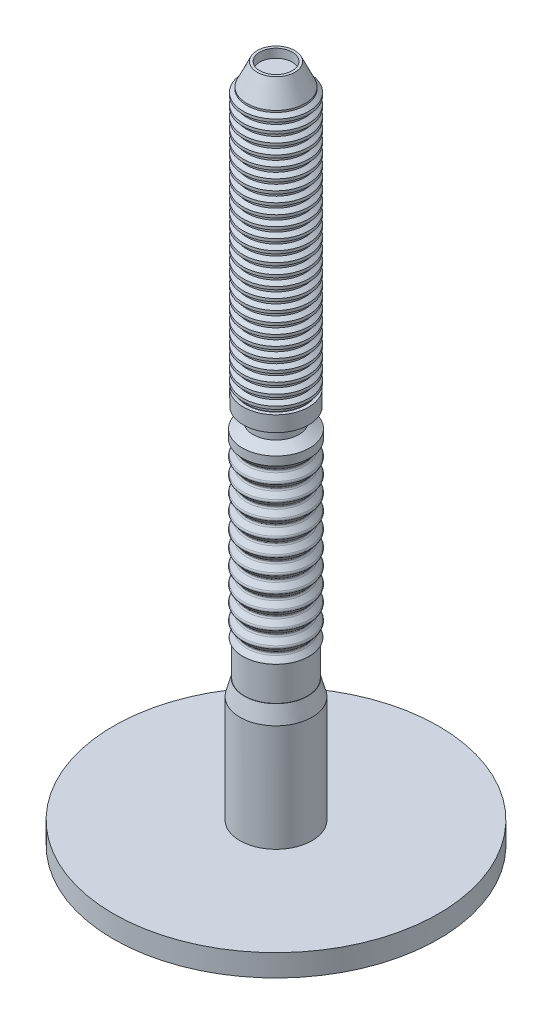
SolidWorks part; units mm, degrees
ref_plane "Front Plane" through (0, 0, 0) normal (0, 0, 1) x (1, 0, 0)
ref_plane "Top Plane" through (0, 0, 0) normal (0, 1, 0) x (1, 0, 0)
ref_plane "Right Plane" through (0, 0, 0) normal (1, 0, 0) x (0, 0, -1)
sketch "Sketch1" plane through (0, 0, 0) normal (0, 1, 0) x (1, 0, 0)
  circle A0 centre (0, 0) radius 18.5
  dimension "D1" = 37
extrude "Boss-Extrude1" add sketch "Sketch1" along normal blind 2.5
sketch "Sketch2" plane through (0, 2.5, 0) normal (0, 1, 0) x (1, 0, 0)
  circle A0 centre (0, 0) radius 4.1
  dimension "D1" = 8.2
extrude "Boss-Extrude2" add sketch "Sketch2" along normal blind 14
sketch "Sketch3" plane through (0, 16.5, 0) normal (0, 1, 0) x (1, 0, 0)
  circle A0 centre (0, 0) radius 3.575
  dimension "D1" = 7.15
extrude "Boss-Extrude3" add sketch "Sketch3" along normal blind 4
sketch "Sketch4" plane through (0, 20.5, 0) normal (0, 1, 0) x (1, 0, 0)
  circle A0 centre (0, 0) radius 3.825
  dimension "D1" = 7.65
extrude "Boss-Extrude4" add sketch "Sketch4" along normal blind 21.3
sketch "Sketch5" plane through (0, 41.8, 0) normal (0, 1, 0) x (1, 0, 0)
  circle A0 centre (0, 0) radius 2.6
  dimension "D1" = 5.2
extrude "Boss-Extrude5" add sketch "Sketch5" along normal blind 0.75
sketch "Sketch6" plane through (0, 42.55, 0) normal (0, 1, 0) x (1, 0, 0)
  circle A0 centre (0, 0) radius 3.725
  dimension "D1" = 7.45
extrude "Boss-Extrude6" add sketch "Sketch6" along normal blind 2.5
sketch "Sketch7" plane through (0, 45.05, 0) normal (0, 1, 0) x (1, 0, 0)
  circle A0 centre (0, 0) radius 3.75
  dimension "D1" = 7.5
extrude "Boss-Extrude7" add sketch "Sketch7" along normal blind 32.2
chamfer "Chamfer2" distance 0.739 angle 60 1 edges at (0, 41.8, 3.825) first distance on face at (0, 41.8, 3.825)
chamfer "Chamfer3" distance 0.739 angle 60 1 edges at (0, 42.55, 3.725) first distance on face at (0, 45.05, 3.725)
chamfer "Chamfer4" distance 1.835 angle 15 1 edges at (0, 16.5, 4.1) first distance on face at (0, 16.5, 4.1)
sketch "Sketch12" plane through (0, 0, 0) normal (0, 0, 1) x (1, 0, 0)
  line L0 (3.244, 25.0466) -> (-3.244, 25.0466) construction
  line L1 (0, 0) -> (0, 79.9408) construction
  line L2 (-3.825, 41.061) -> (-3.825, 40.061)
  line L3 (-3.825, 20.5) -> (3.825, 20.5) construction
  line L4 (-3.244, 20.5) -> (-3.244, 41.061) construction
  line L5 (-3.825, 41.061) -> (3.825, 41.061) construction
  line L6 (-3.825, 40.061) -> (-3.3171, 39.4557)
  line L7 (-3.575, 20.5) -> (3.575, 20.5) construction
  line L8 (3.244, 20.5) -> (3.244, 41.061) construction
  line L9 (-3.244, 39.2549) -> (-3.244, 39.2518)
  line L10 (-3.3171, 39.051) -> (-3.7656, 38.5164)
  line L11 (-3.3171, 37.251) -> (-3.7656, 36.7164)
  line L12 (-3.7656, 36.3903) -> (-3.3171, 35.8557)
  line L13 (-3.7656, 38.1903) -> (-3.3171, 37.6557)
  line L14 (-3.3171, 35.451) -> (-3.7656, 34.9164)
  line L15 (-3.7656, 34.5903) -> (-3.3171, 34.0557)
  line L16 (-3.3171, 33.651) -> (-3.7656, 33.1164)
  line L17 (-3.7656, 32.7903) -> (-3.3171, 32.2557)
  line L18 (-3.3171, 31.851) -> (-3.7656, 31.3164)
  line L19 (-3.7656, 30.9903) -> (-3.3171, 30.4557)
  line L20 (-3.3171, 30.051) -> (-3.7656, 29.5164)
  line L21 (-3.7656, 29.1903) -> (-3.3171, 28.6557)
  line L22 (-3.3171, 28.251) -> (-3.7656, 27.7164)
  line L23 (-3.7656, 27.3903) -> (-3.3171, 26.8557)
  line L24 (-3.3171, 26.451) -> (-3.7656, 25.9164)
  line L25 (-3.7656, 25.5903) -> (-3.3171, 25.0557)
  line L26 (-3.3171, 24.651) -> (-3.7656, 24.1164)
  line L27 (-3.7656, 23.7903) -> (-3.3171, 23.2557)
  line L28 (-3.3171, 22.851) -> (-3.7656, 22.3164)
  line L29 (-3.7656, 21.9903) -> (-3.3171, 21.4557)
  line L30 (-3.3171, 21.051) -> (-3.7656, 20.5164)
  line L31 (-3.244, 21.2518) -> (-3.244, 21.2549)
  line L32 (-3.7656, 20.1903) -> (-3.244, 19.5686) [skipped]
  line L33 (-3.7783, 20.5) -> (-4.0498, 20.5)
  line L34 (-4.0498, 20.5) -> (-4.0498, 41.061)
  line L35 (-4.0498, 41.061) -> (-3.825, 41.061)
  line L36 (-3.244, 23.0518) -> (-3.244, 23.0549)
  line L37 (-3.244, 24.8518) -> (-3.244, 24.8549)
  line L38 (-3.244, 26.6518) -> (-3.244, 26.6549)
  line L39 (-3.244, 28.4518) -> (-3.244, 28.4549)
  line L40 (-3.244, 30.2518) -> (-3.244, 30.2549)
  line L41 (-3.244, 32.0518) -> (-3.244, 32.0549)
  line L42 (-3.244, 33.8518) -> (-3.244, 33.8549)
  line L43 (-3.244, 35.6518) -> (-3.244, 35.6549)
  line L44 (-3.244, 37.4518) -> (-3.244, 37.4549)
  arc A0 (-3.7656, 38.5164) -> (-3.7656, 38.1903) centre (-3.5713, 38.3533) ccw
  arc A1 (-3.244, 39.2518) -> (-3.3171, 39.051) centre (-3.5565, 39.2518) cw
  arc A2 (-3.3171, 39.4557) -> (-3.244, 39.2549) centre (-3.5565, 39.2549) cw
  arc A3 (-3.3171, 37.6557) -> (-3.244, 37.4549) centre (-3.5565, 37.4549) cw
  arc A4 (-3.244, 37.4518) -> (-3.3171, 37.251) centre (-3.5565, 37.4518) cw
  arc A5 (-3.7656, 36.7164) -> (-3.7656, 36.3903) centre (-3.5713, 36.5533) ccw
  arc A6 (-3.3171, 35.8557) -> (-3.244, 35.6549) centre (-3.5565, 35.6549) cw
  arc A7 (-3.244, 35.6518) -> (-3.3171, 35.451) centre (-3.5565, 35.6518) cw
  arc A8 (-3.7656, 34.9164) -> (-3.7656, 34.5903) centre (-3.5713, 34.7533) ccw
  arc A9 (-3.3171, 34.0557) -> (-3.244, 33.8549) centre (-3.5565, 33.8549) cw
  arc A10 (-3.244, 33.8518) -> (-3.3171, 33.651) centre (-3.5565, 33.8518) cw
  arc A11 (-3.7656, 33.1164) -> (-3.7656, 32.7903) centre (-3.5713, 32.9533) ccw
  arc A12 (-3.3171, 32.2557) -> (-3.244, 32.0549) centre (-3.5565, 32.0549) cw
  arc A13 (-3.244, 32.0518) -> (-3.3171, 31.851) centre (-3.5565, 32.0518) cw
  arc A14 (-3.7656, 31.3164) -> (-3.7656, 30.9903) centre (-3.5713, 31.1533) ccw
  arc A15 (-3.3171, 30.4557) -> (-3.244, 30.2549) centre (-3.5565, 30.2549) cw
  arc A16 (-3.244, 30.2518) -> (-3.3171, 30.051) centre (-3.5565, 30.2518) cw
  arc A17 (-3.7656, 29.5164) -> (-3.7656, 29.1903) centre (-3.5713, 29.3533) ccw
  arc A18 (-3.3171, 28.6557) -> (-3.244, 28.4549) centre (-3.5565, 28.4549) cw
  arc A19 (-3.244, 28.4518) -> (-3.3171, 28.251) centre (-3.5565, 28.4518) cw
  arc A20 (-3.7656, 27.7164) -> (-3.7656, 27.3903) centre (-3.5713, 27.5533) ccw
  arc A21 (-3.3171, 26.8557) -> (-3.244, 26.6549) centre (-3.5565, 26.6549) cw
  arc A22 (-3.244, 26.6518) -> (-3.3171, 26.451) centre (-3.5565, 26.6518) cw
  arc A23 (-3.7656, 25.9164) -> (-3.7656, 25.5903) centre (-3.5713, 25.7533) ccw
  arc A24 (-3.3171, 25.0557) -> (-3.244, 24.8549) centre (-3.5565, 24.8549) cw
  arc A25 (-3.244, 24.8518) -> (-3.3171, 24.651) centre (-3.5565, 24.8518) cw
  arc A26 (-3.7656, 24.1164) -> (-3.7656, 23.7903) centre (-3.5713, 23.9533) ccw
  arc A27 (-3.3171, 23.2557) -> (-3.244, 23.0549) centre (-3.5565, 23.0549) cw
  arc A28 (-3.244, 23.0518) -> (-3.3171, 22.851) centre (-3.5565, 23.0518) cw
  arc A29 (-3.7656, 22.3164) -> (-3.7656, 21.9903) centre (-3.5713, 22.1533) ccw
  arc A30 (-3.3171, 21.4557) -> (-3.244, 21.2549) centre (-3.5565, 21.2549) cw
  arc A31 (-3.244, 21.2518) -> (-3.3171, 21.051) centre (-3.5565, 21.2518) cw
  arc A32 (-3.7656, 20.5164) -> (-3.7783, 20.5) centre (-3.5713, 20.3533) ccw
  point P3 (0, 25.0466)
  point P24 (-3.244, 39.1381)
  point P30 (-3.244, 39.3686)
  dimension "D9" = 0.2537
  dimension "D10" = 0.3125
  dimension "D1" = 6.488
  dimension "D2" = 0
  dimension "D3" = 1
  dimension "D5" = 140
  dimension "D6" = 140
  dimension "D7" = 0.2305
  dimension "D8" = 140
  dimension "D11" = 11
revolve "Cut-Revolve1" cut sketch "Sketch12" angle 360 about L1
sketch "Sketch13" plane through (0, 0, 0) normal (0, 0, 1) x (1, 0, 0)
  line L0 (0, 0) -> (0, 79.8538) construction
  line L1 (-3.3095, 50.5688) -> (3.3095, 50.5688) construction
  line L2 (3.3095, 50.5688) -> (3.3095, 81.5967) construction
  line L3 (3.3095, 74.55) -> (3.75, 74.216)
  line L4 (3.75, 45.05) -> (3.75, 77.25) construction
  line L6 (3.3095, 75.05) -> (3.3095, 74.55)
  line L7 (3.75, 74.216) -> (3.75, 73.897)
  line L8 (3.75, 73.897) -> (3.3095, 73.72)
  line L9 (3.3095, 73.72) -> (3.3095, 73.371)
  line L10 (3.3095, 72.541) -> (3.3095, 72.192)
  line L11 (3.75, 72.718) -> (3.3095, 72.541)
  line L12 (3.75, 73.037) -> (3.75, 72.718)
  line L13 (3.3095, 73.371) -> (3.75, 73.037)
  line L14 (3.3095, 71.362) -> (3.3095, 71.013)
  line L15 (3.75, 71.539) -> (3.3095, 71.362)
  line L16 (3.75, 71.858) -> (3.75, 71.539)
  line L17 (3.3095, 72.192) -> (3.75, 71.858)
  line L18 (3.3095, 70.183) -> (3.3095, 69.834)
  line L19 (3.75, 70.36) -> (3.3095, 70.183)
  line L20 (3.75, 70.679) -> (3.75, 70.36)
  line L21 (3.3095, 71.013) -> (3.75, 70.679)
  line L22 (3.3095, 69.004) -> (3.3095, 68.655)
  line L23 (3.75, 69.181) -> (3.3095, 69.004)
  line L24 (3.75, 69.5) -> (3.75, 69.181)
  line L25 (3.3095, 69.834) -> (3.75, 69.5)
  line L26 (3.3095, 67.825) -> (3.3095, 67.476)
  line L27 (3.75, 68.002) -> (3.3095, 67.825)
  line L28 (3.75, 68.321) -> (3.75, 68.002)
  line L29 (3.3095, 68.655) -> (3.75, 68.321)
  line L30 (3.3095, 66.646) -> (3.3095, 66.297)
  line L31 (3.75, 66.823) -> (3.3095, 66.646)
  line L32 (3.75, 67.142) -> (3.75, 66.823)
  line L33 (3.3095, 67.476) -> (3.75, 67.142)
  line L34 (3.3095, 65.467) -> (3.3095, 65.118)
  line L35 (3.75, 65.644) -> (3.3095, 65.467)
  line L36 (3.75, 65.963) -> (3.75, 65.644)
  line L37 (3.3095, 66.297) -> (3.75, 65.963)
  line L38 (3.3095, 64.288) -> (3.3095, 63.939)
  line L39 (3.75, 64.465) -> (3.3095, 64.288)
  line L40 (3.75, 64.784) -> (3.75, 64.465)
  line L41 (3.3095, 65.118) -> (3.75, 64.784)
  line L42 (3.3095, 63.109) -> (3.3095, 62.76)
  line L43 (3.75, 63.286) -> (3.3095, 63.109)
  line L44 (3.75, 63.605) -> (3.75, 63.286)
  line L45 (3.3095, 63.939) -> (3.75, 63.605)
  line L46 (3.3095, 61.93) -> (3.3095, 61.581)
  line L47 (3.75, 62.107) -> (3.3095, 61.93)
  line L48 (3.75, 62.426) -> (3.75, 62.107)
  line L49 (3.3095, 62.76) -> (3.75, 62.426)
  line L50 (3.3095, 60.751) -> (3.3095, 60.402)
  line L51 (3.75, 60.928) -> (3.3095, 60.751)
  line L52 (3.75, 61.247) -> (3.75, 60.928)
  line L53 (3.3095, 61.581) -> (3.75, 61.247)
  line L54 (3.3095, 59.572) -> (3.3095, 59.223)
  line L55 (3.75, 59.749) -> (3.3095, 59.572)
  line L56 (3.75, 60.068) -> (3.75, 59.749)
  line L57 (3.3095, 60.402) -> (3.75, 60.068)
  line L58 (3.3095, 58.393) -> (3.3095, 58.044)
  line L59 (3.75, 58.57) -> (3.3095, 58.393)
  line L60 (3.75, 58.889) -> (3.75, 58.57)
  line L61 (3.3095, 59.223) -> (3.75, 58.889)
  line L62 (3.3095, 57.214) -> (3.3095, 56.865)
  line L63 (3.75, 57.391) -> (3.3095, 57.214)
  line L64 (3.75, 57.71) -> (3.75, 57.391)
  line L65 (3.3095, 58.044) -> (3.75, 57.71)
  line L66 (3.3095, 56.035) -> (3.3095, 55.686)
  line L67 (3.75, 56.212) -> (3.3095, 56.035)
  line L68 (3.75, 56.531) -> (3.75, 56.212)
  line L69 (3.3095, 56.865) -> (3.75, 56.531)
  line L70 (3.3095, 54.856) -> (3.3095, 54.507)
  line L71 (3.75, 55.033) -> (3.3095, 54.856)
  line L72 (3.75, 55.352) -> (3.75, 55.033)
  line L73 (3.3095, 55.686) -> (3.75, 55.352)
  line L74 (3.3095, 53.677) -> (3.3095, 53.328)
  line L75 (3.75, 53.854) -> (3.3095, 53.677)
  line L76 (3.75, 54.173) -> (3.75, 53.854)
  line L77 (3.3095, 54.507) -> (3.75, 54.173)
  line L78 (3.3095, 52.498) -> (3.3095, 52.149)
  line L79 (3.75, 52.675) -> (3.3095, 52.498)
  line L80 (3.75, 52.994) -> (3.75, 52.675)
  line L81 (3.3095, 53.328) -> (3.75, 52.994)
  line L82 (3.3095, 51.319) -> (3.3095, 50.97)
  line L83 (3.75, 51.496) -> (3.3095, 51.319)
  line L84 (3.75, 51.815) -> (3.75, 51.496)
  line L85 (3.3095, 52.149) -> (3.75, 51.815)
  line L86 (3.3095, 50.14) -> (3.3095, 49.791)
  line L87 (3.75, 50.317) -> (3.3095, 50.14)
  line L88 (3.75, 50.636) -> (3.75, 50.317)
  line L89 (3.3095, 50.97) -> (3.75, 50.636)
  line L90 (3.3095, 48.961) -> (3.3095, 48.612)
  line L91 (3.75, 49.138) -> (3.3095, 48.961)
  line L92 (3.75, 49.457) -> (3.75, 49.138)
  line L93 (3.3095, 49.791) -> (3.75, 49.457)
  line L94 (3.3095, 47.782) -> (3.3095, 47.433)
  line L95 (3.75, 47.959) -> (3.3095, 47.782)
  line L96 (3.75, 48.278) -> (3.75, 47.959)
  line L97 (3.3095, 48.612) -> (3.75, 48.278)
  line L98 (3.3095, 46.603) -> (3.3095, 46.254)
  line L99 (3.75, 46.78) -> (3.3095, 46.603)
  line L100 (3.75, 47.099) -> (3.75, 46.78)
  line L101 (3.3095, 47.433) -> (3.75, 47.099)
  line L102 (3.3095, 45.424) -> (3.3095, 45.075)
  line L103 (3.75, 45.601) -> (3.3095, 45.424)
  line L104 (3.75, 45.92) -> (3.75, 45.601)
  line L105 (3.3095, 46.254) -> (3.75, 45.92)
  line L106 (3.75, 45.05) -> (5.1368, 45.05)
  line L107 (5.1368, 45.05) -> (5.1368, 75.05)
  line L109 (3.3095, 45.075) -> (3.3425, 45.05)
  line L110 (3.75, 45.05) -> (3.3425, 45.05)
  line L112 (3.3095, 75.05) -> (3.3095, 77.6165)
  line L113 (3.75, 44.741) -> (3.75, 44.422) [skipped]
  line L114 (3.75, 44.422) -> (3.3095, 44.245) [skipped]
  line L115 (3.3095, 44.245) -> (3.3095, 43.896) [skipped]
  line L116 (3.3095, 77.6165) -> (5.1368, 77.6165)
  line L117 (5.1368, 77.6165) -> (5.1368, 75.05)
  point P6 (0, 50.5688)
  dimension "D1" = 6.619
  dimension "D2" = 0.5
  dimension "D3" = 0.334
  dimension "D4" = 0.319
  dimension "D5" = 0.177
  dimension "D6" = 0.349
  dimension "D7" = 26
revolve "Cut-Revolve2" cut sketch "Sketch13" angle 360 about L0
chamfer "Chamfer5" distance 2.5 angle 25 1 edges at (0, 77.25, 3.3095) first distance on face at (0, 77.25, 3.3095)
sketch "Sketch14" plane through (0, 77.25, 0) normal (0, 1, 0) x (1, 0, 0)
  circle A2 centre (0, 0) radius 1.8437
  circle A3 centre (0, 0) radius 1.8437
  dimension "D1" = 0.3
extrude "Cut-Extrude2" cut sketch "Sketch14" against normal blind 1
